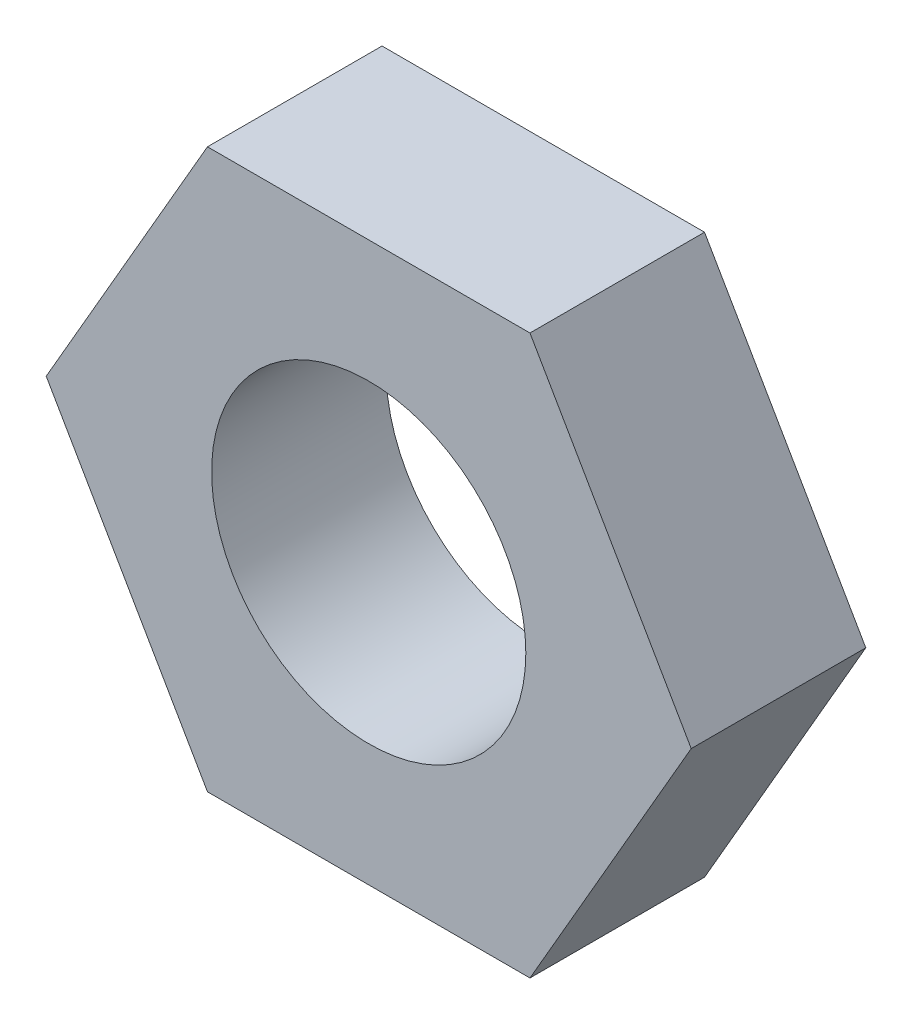
SolidWorks part; units mm, degrees
ref_plane "Front" through (0, 0, 0) normal (0, 0, 1) x (1, 0, 0)
ref_plane "Top" through (0, 0, 0) normal (0, 1, 0) x (1, 0, 0)
ref_plane "Right" through (0, 0, 0) normal (1, 0, 0) x (0, 0, -1)
sketch "Sketch1" plane through (0, 0, 0) normal (0, 0, 1) x (1, 0, 0)
  line L1 (4.6188, -8) -> (9.2376, 0)
  line L2 (9.2376, 0) -> (4.6188, 8)
  line L3 (4.6188, 8) -> (-4.6188, 8)
  line L4 (-4.6188, 8) -> (-9.2376, 0)
  line L5 (-9.2376, 0) -> (-4.6188, -8)
  line L6 (-4.6188, -8) -> (4.6188, -8)
  circle A0 centre (0, 0) radius 8 construction
  circle A1 centre (0, 0) radius 4.5
  dimension "D1" = 9
extrude "BaseNut" add sketch "Sketch1" against normal blind 5
cosmetic thread "ThreadCosmetic1" [suppressed] parameters "D2"=10
sketch "Sketch2" plane through (0, 0, 0) normal (0, 1, 0) x (1, 0, 0)
  line L0 (0, 7.0076) -> (0, -1.3024) construction
  line L1 (4, 5.25) -> (4.5, 5.25)
  line L2 (4.5, 5.25) -> (4.933, 5)
  line L3 (4.933, 5) -> (4.5, 4.75)
  line L4 (4.5, 4.75) -> (4, 4.75)
  line L5 (4, 4.75) -> (4, 5.25)
  line L6 (9.2376, 5) -> (4.6188, 5) construction
  dimension "D1" = 0.5
  dimension "D2" = 9
revolve "Cut-Revolve10" [suppressed] cut sketch "Sketch2" angle 360 about L0
pattern_linear "LPattern10" [suppressed] count 8 spacing 0.6 along (0, 0, 1) of bodies 102
equation "\"D1@Sketch2\" =  ( \"D2@ThreadCosmetic1\" - \"D1@Sketch1\" )  / 2"
equation "\"D2@Sketch2\" = \"D1@Sketch1\""
equation "\"D3@LPattern10\" = \"D1@Sketch2\" * 1.2"
equation "\"D1@LPattern10\" = \"m@BaseNut\" / \"D3@LPattern10\""
